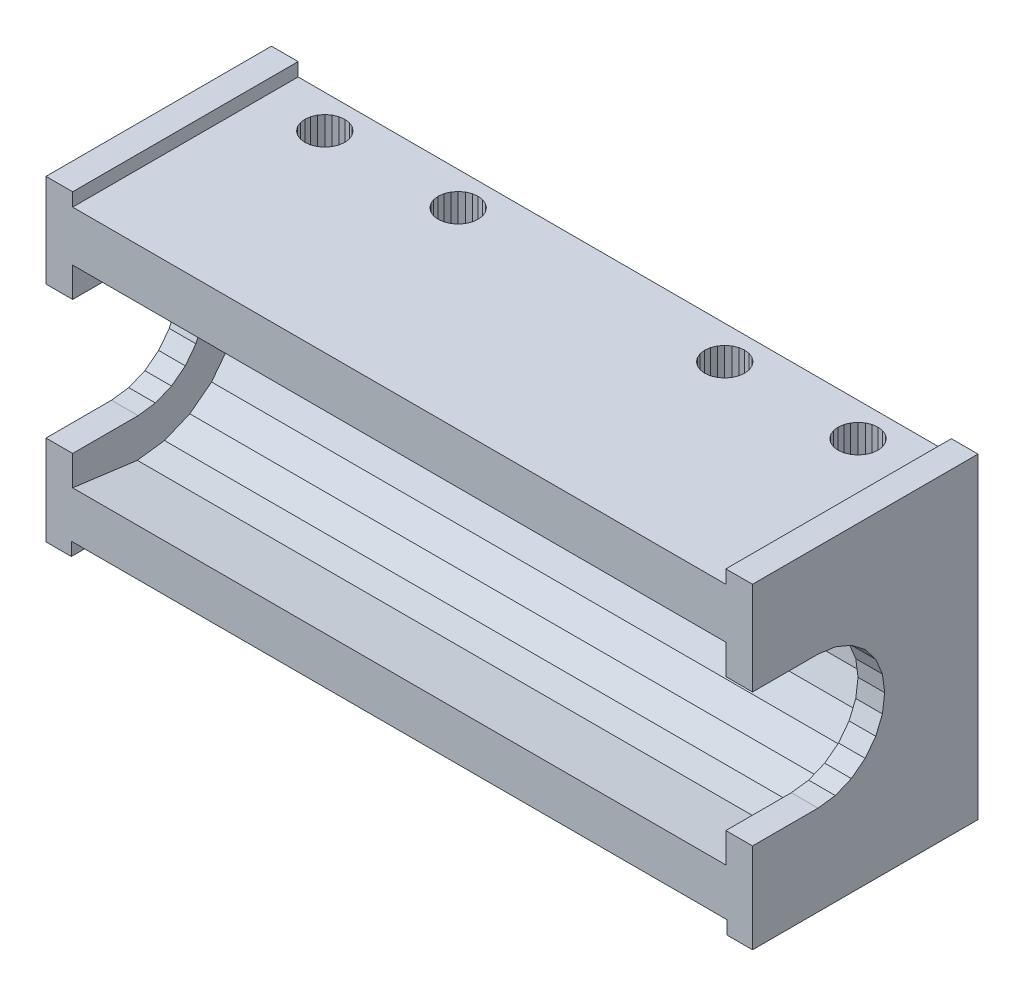
SolidWorks part; units mm, degrees
ref_plane "Front Plane" through (0, 0, 0) normal (0, 0, 1) x (1, 0, 0)
ref_plane "Top Plane" through (0, 0, 0) normal (0, 1, 0) x (1, 0, 0)
ref_plane "Right Plane" through (0, 0, 0) normal (1, 0, 0) x (0, 0, -1)
ref_plane "Plane1" through (0, 0, 0) normal (0, 0, -1) x (-1, 0, 0)
sketch "Sketch1" plane through (0, 0, 0) normal (0, 0, -1) x (-1, 0, 0)
  line L0 (-106, 86.875) -> (-106, 63.125)
  line L1 (-106, 63.125) -> (-53, 63.125)
  line L2 (-53, 63.125) -> (-53, 86.875)
  line L3 (-53, 86.875) -> (-106, 86.875)
extrude "Boss-Extrude1" add sketch "Sketch1" against normal blind 16.9155
sketch "Sketch2" plane through (0, 0, 16.9155) normal (0, 0, 1) x (1, 0, 0)
  line L0 (54.9, 63.125) -> (104.1, 63.125)
  line L1 (104.1, 63.125) -> (104.1, 64.125)
  line L2 (104.1, 64.125) -> (54.9, 64.125)
  line L3 (54.9, 64.125) -> (54.9, 63.125)
extrude "Cut-Extrude1" cut sketch "Sketch2" against normal through all
sketch "Sketch3" plane through (0, 64.125, 0) normal (0, -1, 0) x (1, 0, 0)
  line L0 (91.7453, 0) -> (91.7453, 0.5)
  line L1 (91.7453, 0.5) -> (92.9, 2.5)
  line L2 (92.9, 2.5) -> (91.2, 5.4445)
  line L3 (91.2, 5.4445) -> (87.8, 5.4445)
  line L4 (87.8, 5.4445) -> (86.1, 2.5)
  line L5 (86.1, 2.5) -> (87.2547, 0.5)
  line L6 (87.2547, 0.5) -> (87.2547, 0)
  line L7 (87.2547, 0) -> (91.7453, 0)
extrude "Cut-Extrude2" cut sketch "Sketch3" against normal blind 5
sketch "Sketch4" plane through (0, 64.125, 0) normal (0, -1, 0) x (1, 0, 0)
  line L0 (67.2547, 0.5) -> (67.2547, 0)
  line L1 (67.2547, 0) -> (71.7453, 0)
  line L2 (71.7453, 0) -> (71.7453, 0.5)
  line L3 (71.7453, 0.5) -> (72.9, 2.5)
  line L4 (72.9, 2.5) -> (71.2, 5.4445)
  line L5 (71.2, 5.4445) -> (67.8, 5.4445)
  line L6 (67.8, 5.4445) -> (66.1, 2.5)
  line L7 (66.1, 2.5) -> (67.2547, 0.5)
extrude "Cut-Extrude3" cut sketch "Sketch4" against normal blind 5
sketch "Sketch5" plane through (0, 0, 0) normal (0, 0, -1) x (-1, 0, 0)
  line L0 (-55, 86.875) -> (-104, 86.875)
  line L1 (-104, 86.875) -> (-104, 85.875)
  line L2 (-104, 85.875) -> (-55, 85.875)
  line L3 (-55, 85.875) -> (-55, 86.875)
extrude "Cut-Extrude4" cut sketch "Sketch5" against normal through all
ref_plane "Plane2" through (104, 0, 0) normal (1, 0, 0) x (0, 0, -1)
sketch "Sketch6" plane through (104, 0, 0) normal (1, 0, 0) x (0, 0, -1)
  line L0 (-16.9155, 82.1114) -> (-16.9155, 67.6386)
  line L1 (-16.9155, 67.6386) -> (-12.0646, 67)
  line L2 (-12.0646, 67) -> (-10.0264, 67.2683)
  line L3 (-10.0264, 67.2683) -> (-8.1271, 68.055)
  line L4 (-8.1271, 68.055) -> (-6.4961, 69.3065)
  line L5 (-6.4961, 69.3065) -> (-5.2447, 70.9375)
  line L6 (-5.2447, 70.9375) -> (-4.4579, 72.8368)
  line L7 (-4.4579, 72.8368) -> (-4.1896, 74.875)
  line L8 (-4.1896, 74.875) -> (-4.4579, 76.9132)
  line L9 (-4.4579, 76.9132) -> (-5.2447, 78.8125)
  line L10 (-5.2447, 78.8125) -> (-6.4961, 80.4435)
  line L11 (-6.4961, 80.4435) -> (-8.1271, 81.6949)
  line L12 (-8.1271, 81.6949) -> (-10.0264, 82.4817)
  line L13 (-10.0264, 82.4817) -> (-12.0646, 82.75)
  line L14 (-12.0646, 82.75) -> (-16.9155, 82.1114)
extrude "Cut-Extrude5" cut sketch "Sketch6" against normal blind 49
sketch "Sketch7" plane through (104, 0, 0) normal (-1, 0, 0) x (0, 0, 1)
  line L0 (16.9155, 69.875) -> (16.9155, 79.875)
  line L1 (16.9155, 79.875) -> (12, 79.875)
  line L2 (12, 79.875) -> (10.7059, 79.7046)
  line L3 (10.7059, 79.7046) -> (9.5, 79.2051)
  line L4 (9.5, 79.2051) -> (8.4645, 78.4105)
  line L5 (8.4645, 78.4105) -> (7.6699, 77.375)
  line L6 (7.6699, 77.375) -> (7.1704, 76.1691)
  line L7 (7.1704, 76.1691) -> (7, 74.875)
  line L8 (7, 74.875) -> (7.1704, 73.5809)
  line L9 (7.1704, 73.5809) -> (7.6699, 72.375)
  line L10 (7.6699, 72.375) -> (8.4645, 71.3395)
  line L11 (8.4645, 71.3395) -> (9.5, 70.5449)
  line L12 (9.5, 70.5449) -> (10.7059, 70.0454)
  line L13 (10.7059, 70.0454) -> (12, 69.875)
  line L14 (12, 69.875) -> (16.9155, 69.875)
extrude "Cut-Extrude6" cut sketch "Sketch7" against normal through all
sketch "Sketch8" plane through (55, 0, 0) normal (1, 0, 0) x (0, 0, -1)
  line L0 (-16.9155, 79.875) -> (-16.9155, 69.875)
  line L1 (-16.9155, 69.875) -> (-12, 69.875)
  line L2 (-12, 69.875) -> (-10.7059, 70.0454)
  line L3 (-10.7059, 70.0454) -> (-9.5, 70.5449)
  line L4 (-9.5, 70.5449) -> (-8.4645, 71.3395)
  line L5 (-8.4645, 71.3395) -> (-7.6699, 72.375)
  line L6 (-7.6699, 72.375) -> (-7.1704, 73.5809)
  line L7 (-7.1704, 73.5809) -> (-7, 74.875)
  line L8 (-7, 74.875) -> (-7.1704, 76.1691)
  line L9 (-7.1704, 76.1691) -> (-7.6699, 77.375)
  line L10 (-7.6699, 77.375) -> (-8.4645, 78.4105)
  line L11 (-8.4645, 78.4105) -> (-9.5, 79.2051)
  line L12 (-9.5, 79.2051) -> (-10.7059, 79.7046)
  line L13 (-10.7059, 79.7046) -> (-12, 79.875)
  line L14 (-12, 79.875) -> (-16.9155, 79.875)
extrude "Cut-Extrude7" cut sketch "Sketch8" against normal through all
sketch "Sketch9" plane through (0, 85.875, 0) normal (0, 1, 0) x (-1, 0, 0)
  line L0 (-98.0511, 2.8882) -> (-98.201, 3.25)
  line L1 (-98.201, 3.25) -> (-98.4393, 3.5607)
  line L2 (-98.4393, 3.5607) -> (-98.75, 3.799)
  line L3 (-98.75, 3.799) -> (-99.1118, 3.9489)
  line L4 (-99.1118, 3.9489) -> (-99.5, 4)
  line L5 (-99.5, 4) -> (-99.8882, 3.9489)
  line L6 (-99.8882, 3.9489) -> (-100.25, 3.799)
  line L7 (-100.25, 3.799) -> (-100.5607, 3.5607)
  line L8 (-100.5607, 3.5607) -> (-100.799, 3.25)
  line L9 (-100.799, 3.25) -> (-100.9489, 2.8882)
  line L10 (-100.9489, 2.8882) -> (-101, 2.5)
  line L11 (-101, 2.5) -> (-100.9489, 2.1118)
  line L12 (-100.9489, 2.1118) -> (-100.799, 1.75)
  line L13 (-100.799, 1.75) -> (-100.5607, 1.4393)
  line L14 (-100.5607, 1.4393) -> (-100.25, 1.201)
  line L15 (-100.25, 1.201) -> (-99.8882, 1.0511)
  line L16 (-99.8882, 1.0511) -> (-99.5, 1)
  line L17 (-99.5, 1) -> (-99.1118, 1.0511)
  line L18 (-99.1118, 1.0511) -> (-98.75, 1.201)
  line L19 (-98.75, 1.201) -> (-98.4393, 1.4393)
  line L20 (-98.4393, 1.4393) -> (-98.201, 1.75)
  line L21 (-98.201, 1.75) -> (-98.0511, 2.1118)
  line L22 (-98.0511, 2.1118) -> (-98, 2.5)
  line L23 (-98, 2.5) -> (-98.0511, 2.8882)
extrude "Cut-Extrude8" cut sketch "Sketch9" against normal through all
sketch "Sketch10" plane through (0, 85.875, 0) normal (0, 1, 0) x (-1, 0, 0)
  line L0 (-70.799, 3.25) -> (-70.9489, 2.8882)
  line L1 (-70.9489, 2.8882) -> (-71, 2.5)
  line L2 (-71, 2.5) -> (-70.9489, 2.1118)
  line L3 (-70.9489, 2.1118) -> (-70.799, 1.75)
  line L4 (-70.799, 1.75) -> (-70.5607, 1.4393)
  line L5 (-70.5607, 1.4393) -> (-70.25, 1.201)
  line L6 (-70.25, 1.201) -> (-69.8882, 1.0511)
  line L7 (-69.8882, 1.0511) -> (-69.5, 1)
  line L8 (-69.5, 1) -> (-69.1118, 1.0511)
  line L9 (-69.1118, 1.0511) -> (-68.75, 1.201)
  line L10 (-68.75, 1.201) -> (-68.4393, 1.4393)
  line L11 (-68.4393, 1.4393) -> (-68.201, 1.75)
  line L12 (-68.201, 1.75) -> (-68.0511, 2.1118)
  line L13 (-68.0511, 2.1118) -> (-68, 2.5)
  line L14 (-68, 2.5) -> (-68.0511, 2.8882)
  line L15 (-68.0511, 2.8882) -> (-68.201, 3.25)
  line L16 (-68.201, 3.25) -> (-68.4393, 3.5607)
  line L17 (-68.4393, 3.5607) -> (-68.75, 3.799)
  line L18 (-68.75, 3.799) -> (-69.1118, 3.9489)
  line L19 (-69.1118, 3.9489) -> (-69.5, 4)
  line L20 (-69.5, 4) -> (-69.8882, 3.9489)
  line L21 (-69.8882, 3.9489) -> (-70.25, 3.799)
  line L22 (-70.25, 3.799) -> (-70.5607, 3.5607)
  line L23 (-70.5607, 3.5607) -> (-70.799, 3.25)
extrude "Cut-Extrude9" cut sketch "Sketch10" against normal through all
sketch "Sketch11" plane through (0, 85.875, 0) normal (0, 1, 0) x (-1, 0, 0)
  line L0 (-88.0511, 2.8882) -> (-88.201, 3.25)
  line L1 (-88.201, 3.25) -> (-88.4393, 3.5607)
  line L2 (-88.4393, 3.5607) -> (-88.75, 3.799)
  line L3 (-88.75, 3.799) -> (-89.1118, 3.9489)
  line L4 (-89.1118, 3.9489) -> (-89.5, 4)
  line L5 (-89.5, 4) -> (-89.8882, 3.9489)
  line L6 (-89.8882, 3.9489) -> (-90.25, 3.799)
  line L7 (-90.25, 3.799) -> (-90.5607, 3.5607)
  line L8 (-90.5607, 3.5607) -> (-90.799, 3.25)
  line L9 (-90.799, 3.25) -> (-90.9489, 2.8882)
  line L10 (-90.9489, 2.8882) -> (-91, 2.5)
  line L11 (-91, 2.5) -> (-90.9489, 2.1118)
  line L12 (-90.9489, 2.1118) -> (-90.799, 1.75)
  line L13 (-90.799, 1.75) -> (-90.5607, 1.4393)
  line L14 (-90.5607, 1.4393) -> (-90.25, 1.201)
  line L15 (-90.25, 1.201) -> (-89.8882, 1.0511)
  line L16 (-89.8882, 1.0511) -> (-89.5, 1)
  line L17 (-89.5, 1) -> (-89.1118, 1.0511)
  line L18 (-89.1118, 1.0511) -> (-88.75, 1.201)
  line L19 (-88.75, 1.201) -> (-88.4393, 1.4393)
  line L20 (-88.4393, 1.4393) -> (-88.201, 1.75)
  line L21 (-88.201, 1.75) -> (-88.0511, 2.1118)
  line L22 (-88.0511, 2.1118) -> (-88, 2.5)
  line L23 (-88, 2.5) -> (-88.0511, 2.8882)
extrude "Cut-Extrude10" cut sketch "Sketch11" against normal through all
sketch "Sketch12" plane through (0, 64.125, 0) normal (0, -1, 0) x (1, 0, 0)
  line L0 (60.799, 3.25) -> (60.5607, 3.5607)
  line L1 (60.5607, 3.5607) -> (60.25, 3.799)
  line L2 (60.25, 3.799) -> (59.8882, 3.9489)
  line L3 (59.8882, 3.9489) -> (59.5, 4)
  line L4 (59.5, 4) -> (59.1118, 3.9489)
  line L5 (59.1118, 3.9489) -> (58.75, 3.799)
  line L6 (58.75, 3.799) -> (58.4393, 3.5607)
  line L7 (58.4393, 3.5607) -> (58.201, 3.25)
  line L8 (58.201, 3.25) -> (58.0511, 2.8882)
  line L9 (58.0511, 2.8882) -> (58, 2.5)
  line L10 (58, 2.5) -> (58.0511, 2.1118)
  line L11 (58.0511, 2.1118) -> (58.201, 1.75)
  line L12 (58.201, 1.75) -> (58.4393, 1.4393)
  line L13 (58.4393, 1.4393) -> (58.75, 1.201)
  line L14 (58.75, 1.201) -> (59.1118, 1.0511)
  line L15 (59.1118, 1.0511) -> (59.5, 1)
  line L16 (59.5, 1) -> (59.8882, 1.0511)
  line L17 (59.8882, 1.0511) -> (60.25, 1.201)
  line L18 (60.25, 1.201) -> (60.5607, 1.4393)
  line L19 (60.5607, 1.4393) -> (60.799, 1.75)
  line L20 (60.799, 1.75) -> (60.9489, 2.1118)
  line L21 (60.9489, 2.1118) -> (61, 2.5)
  line L22 (61, 2.5) -> (60.9489, 2.8882)
  line L23 (60.9489, 2.8882) -> (60.799, 3.25)
extrude "Cut-Extrude11" cut sketch "Sketch12" against normal through all
